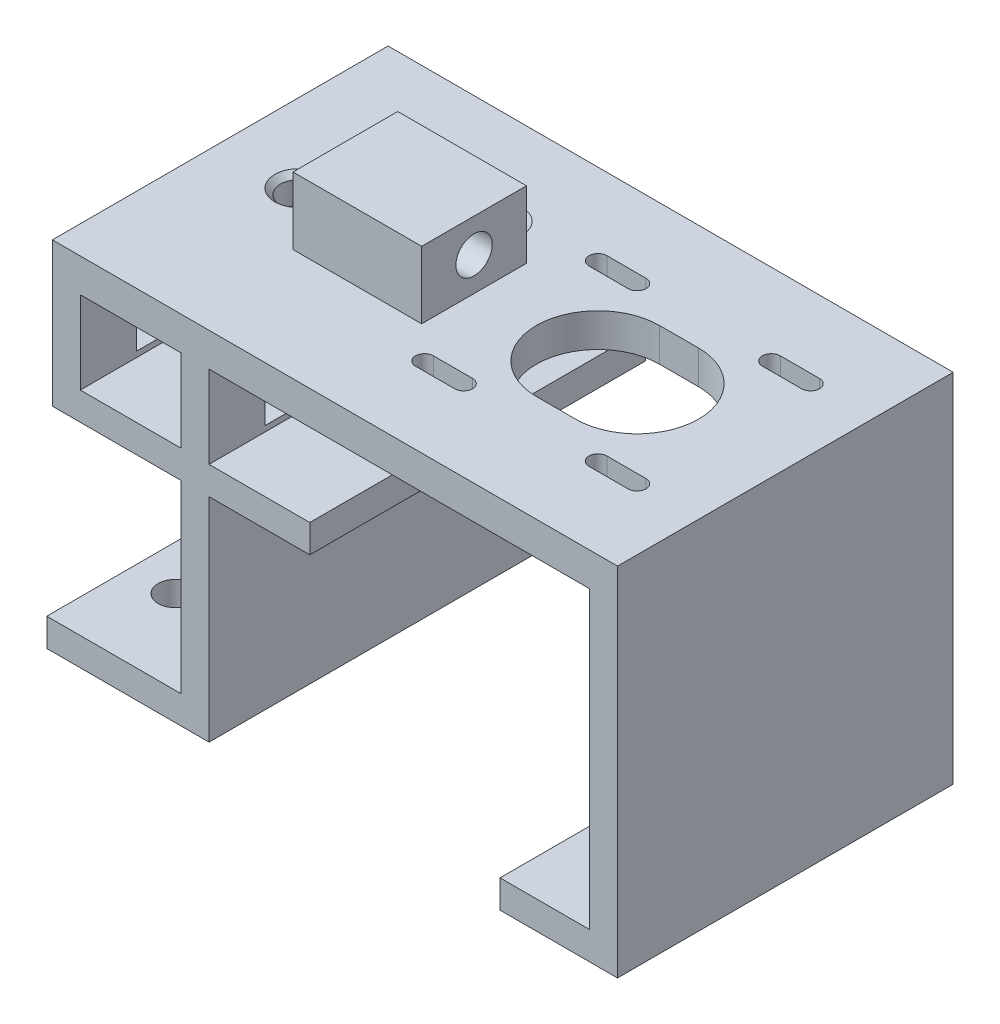
SolidWorks part; units mm, degrees
material "PET"
ref_plane "Front Plane" through (0, 0, 0) normal (0, 0, 1) x (1, 0, 0)
ref_plane "Top Plane" through (0, 0, 0) normal (0, 1, 0) x (1, 0, 0)
ref_plane "Right Plane" through (0, 0, 0) normal (1, 0, 0) x (0, 0, -1)
sketch "Sketch1" plane through (0, 0, 0) normal (0, 0, 1) x (1, 0, 0)
  line L0 (0, 0) -> (-29, 0)
  line L1 (-29, 0) -> (-29, 5)
  line L2 (-29, 5) -> (-5, 5)
  line L3 (-5, 5) -> (-5, 38)
  line L4 (-5, 75.75) -> (18, 75.75)
  line L5 (18, 75.75) -> (18, 63.75)
  line L6 (18, 63.75) -> (73, 63.75)
  line L7 (73, 63.75) -> (73, 0)
  line L10 (73, 0) -> (52, 0)
  line L11 (68, 5) -> (68, 57.75)
  line L12 (68, 57.75) -> (0, 57.75)
  line L13 (0, 57.75) -> (0, 43)
  line L14 (0, 43) -> (18, 43)
  line L15 (18, 43) -> (18, 38)
  line L16 (18, 38) -> (0, 38)
  line L17 (0, 0) -> (0, 38)
  line L18 (-5, 63.75) -> (-28, 63.75)
  line L19 (-28, 63.75) -> (-28, 38)
  line L20 (-28, 38) -> (-5, 38)
  line L21 (-5, 57.75) -> (-23, 57.75)
  line L22 (-23, 57.75) -> (-23, 43)
  line L23 (-23, 43) -> (-5, 43)
  line L24 (-5, 63.75) -> (-5, 75.75)
  line L25 (-5, 43) -> (-5, 57.75)
  line L26 (68, 5) -> (52, 5)
  line L27 (52, 5) -> (52, 0)
  point P19 (0, 19)
  point P28 (-29, 2.5)
  dimension "D1" = 5
  dimension "D2" = 6
  dimension "D3" = 5
  dimension "D4" = 18
  dimension "D5" = 5
  dimension "D6" = 14.75
  dimension "D7" = 43
  dimension "D8" = 5
  dimension "D9" = 50
  dimension "D10" = 21
  dimension "D11" = 23
  dimension "D12" = 12
  dimension "D13" = 23
  dimension "D14" = 5
  dimension "D15" = 5
  dimension "D16" = 24
extrude "Boss-Extrude1" add sketch "Sketch1" along normal blind 60
sketch "Sketch2" plane through (0, 0, 0) normal (1, 0, 0) x (0, 0, -1)
  line L0 (-60, 0) -> (-60, 63.75) construction
  line L1 (-50, 58.75) -> (-10, 58.75)
  line L2 (-50, 58.75) -> (-50, 44)
  line L3 (-50, 44) -> (-10, 44)
  line L4 (-10, 58.75) -> (-10, 44)
  line L5 (-60, 63.75) -> (0, 63.75) construction
  line L6 (0, 0) -> (0, 63.75) construction
  dimension "D1" = 10
  dimension "D2" = 14.75
  dimension "D3" = 5
  dimension "D4" = 10
extrude "Cut-Extrude1" cut sketch "Sketch2" against normal up to next
sketch "Sketch3" plane through (0, 63.75, 0) normal (0, 1, 0) x (1, 0, 0)
  line L0 (18, -30) -> (68, -30) construction
  line L1 (18, -60) -> (18, 0) construction
  line L3 (39.5, -30) -> (46.5, -30) construction
  line L4 (39.5, -19) -> (46.5, -19)
  line L5 (39.5, -41) -> (46.5, -41)
  line L6 (31, -14.5) -> (24, -14.5) construction
  line L7 (31, -16.1) -> (24, -16.1)
  line L8 (31, -12.9) -> (24, -12.9)
  line L9 (43, -30) -> (43, 0) construction
  line L12 (73, 0) -> (18, 0) construction
  line L13 (55, -14.5) -> (62, -14.5) construction
  line L14 (55, -16.1) -> (62, -16.1)
  line L15 (55, -12.9) -> (62, -12.9)
  line L16 (31, -45.5) -> (24, -45.5) construction
  line L17 (31, -43.9) -> (24, -43.9)
  line L18 (31, -47.1) -> (24, -47.1)
  line L19 (55, -45.5) -> (62, -45.5) construction
  line L20 (55, -43.9) -> (62, -43.9)
  line L21 (55, -47.1) -> (62, -47.1)
  arc A0 (39.5, -19) -> (39.5, -41) centre (39.5, -30) ccw
  arc A1 (46.5, -41) -> (46.5, -19) centre (46.5, -30) ccw
  arc A2 (31, -16.1) -> (31, -12.9) centre (31, -14.5) ccw
  arc A3 (24, -12.9) -> (24, -16.1) centre (24, -14.5) ccw
  arc A4 (55, -16.1) -> (55, -12.9) centre (55, -14.5) cw
  arc A5 (62, -12.9) -> (62, -16.1) centre (62, -14.5) cw
  arc A6 (31, -43.9) -> (31, -47.1) centre (31, -45.5) cw
  arc A7 (24, -47.1) -> (24, -43.9) centre (24, -45.5) cw
  arc A8 (55, -43.9) -> (55, -47.1) centre (55, -45.5) ccw
  arc A9 (62, -47.1) -> (62, -43.9) centre (62, -45.5) ccw
  point P8 (43, -30)
  point P15 (27.5, -14.5)
  point P24 (58.5, -14.5)
  point P31 (27.5, -45.5)
  point P38 (58.5, -45.5)
  dimension "D2" = 11
  dimension "D4" = 1.6
  dimension "D1" = 7
  dimension "D3" = 7
  dimension "D5" = 15.5
  dimension "D6" = 15.5
  dimension "D7" = 50
extrude "Cut-Extrude2" cut sketch "Sketch3" against normal up to next
sketch "Sketch5" plane through (0, 75.75, 0) normal (0, 1, 0) x (1, 0, 0)
  line L0 (18, -30) -> (-5, -30) construction
  line L1 (18, -60) -> (18, 0) construction
  line L2 (-5, -60) -> (-5, 0) construction
  line L3 (18, -60) -> (18, 0) construction
  circle A0 centre (9, -17.27) radius 3.25
  dimension "D1" = 6.5
  dimension "D2" = 12.73
  dimension "D3" = 9
extrude "Cut-Extrude3" cut sketch "Sketch5" against normal up to next
sketch "Sketch6" plane through (0, 43, 0) normal (0, 1, 0) x (1, 0, 0)
  circle A0 centre (9, -17.27) radius 2.6
  dimension "D1" = 5.2
extrude "Cut-Extrude4" cut sketch "Sketch6" against normal up to next
sketch "Sketch7" plane through (0, 63.75, 0) normal (0, 1, 0) x (1, 0, 0)
  line L0 (28.5, -30) -> (-28, -30) construction
  line L1 (-28, -60) -> (-28, 0) construction
  line L2 (-5, -60) -> (-5, 0) construction
  arc A0 (39.5, -19) -> (39.5, -41) centre (39.5, -30) ccw construction
  circle A1 centre (-14, -30) radius 2.6
  dimension "D1" = 9
  dimension "D2" = 5.2
extrude "Cut-Extrude5" cut sketch "Sketch7" against normal through all
sketch "Sketch8" plane through (0, 63.75, 0) normal (0, 1, 0) x (1, 0, 0)
  circle A0 centre (-14, -30) radius 3.25
  dimension "D1" = 6.5
extrude "Cut-Extrude6" cut sketch "Sketch8" against normal up to next
sketch "Sketch9" plane through (0, 75.75, 0) normal (0, 1, 0) x (1, 0, 0)
  line L0 (18, -60) -> (18, 0) construction
  line L1 (-5, 0) -> (18, 0)
  line L2 (-5, 0) -> (-5, -21.27)
  line L3 (-5, -21.27) -> (18, -21.27)
  line L4 (18, 0) -> (18, -21.27)
  line L6 (-5, -60) -> (18, -60)
  line L7 (-5, -60) -> (-5, -40)
  line L8 (-5, -40) -> (18, -40)
  line L9 (18, -60) -> (18, -40)
  circle A0 centre (9, -17.27) radius 3.25 construction
  dimension "D1" = 4
  dimension "D2" = 20
extrude "Cut-Extrude7" cut sketch "Sketch9" against normal up to surface (12 mm away) up to face at (58.5, 63.75, 45.5)
chamfer "Chamfer1" distance 1 angle 45 2 edges at (-14, 63.75, 33.25) (9, 63.75, 14.02)
ref_plane "Plane1" through (9, 0, 0) normal (1, 0, 0) x (0, 0, -1)
sketch "Sketch10" plane through (0, 0, 0) normal (0, -1, 0) x (1, 0, 0)
  line L0 (-21, 60) -> (-21, 0) construction
  line L1 (-29, 60) -> (0, 60) construction
  line L2 (-29, 0) -> (0, 0) construction
  line L3 (60, 60) -> (60, 0) construction
  line L4 (52, 60) -> (73, 60) construction
  line L5 (52, 0) -> (73, 0) construction
  line L6 (0, 60) -> (0, 0) construction
  line L7 (-21, 45) -> (60, 45) construction
  line L8 (-29, 30) -> (73, 30) construction
  line L9 (-29, 60) -> (-29, 0) construction
  line L11 (-21, 15) -> (60, 15) construction
  line L12 (73, 60) -> (73, 0) construction
  line L13 (52, 60) -> (52, 0) construction
  circle A0 centre (-21, 45) radius 3.1
  circle A1 centre (-21, 15) radius 3.1
  circle A2 centre (60, 15) radius 2.6
  circle A3 centre (60, 45) radius 2.6
  dimension "D5" = 6.2
  dimension "D6" = 6.2
  dimension "D7" = 5.2
  dimension "D8" = 5.2
  dimension "D1" = 21
  dimension "D2" = 15
  dimension "D3" = 15
  dimension "D4" = 8
extrude "Cut-Extrude8" cut sketch "Sketch10" against normal up to next
sketch "Sketch11" plane through (-5, 0, 0) normal (-1, 0, 0) x (0, 0, 1)
  line L0 (21.27, 63.75) -> (40, 75.75) construction
  line L1 (60, 63.75) -> (0, 63.75) construction
  line L2 (40, 63.75) -> (21.27, 63.75) construction
  circle A0 centre (30.635, 69.75) radius 3.25
  dimension "D1" = 6.5
extrude "Cut-Extrude9" cut sketch "Sketch11" against normal through all
chamfer "Chamfer2" distance 1 angle 45 1 edges at (-5, 66.5, 30.635)
